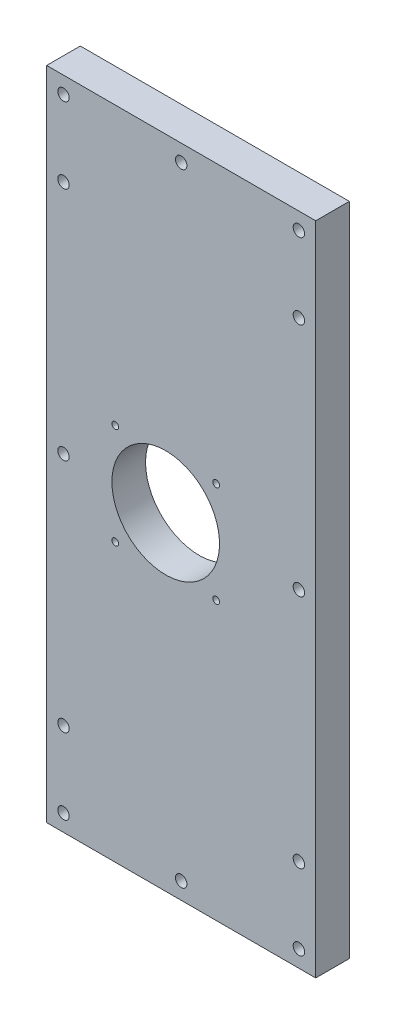
SolidWorks part; units mm, degrees
material "AISI 1020"
ref_plane "Ebene vorne" through (0, 0, 0) normal (0, 0, 1) x (1, 0, 0)
ref_plane "Ebene oben" through (0, 0, 0) normal (0, 1, 0) x (1, 0, 0)
ref_plane "Ebene rechts" through (0, 0, 0) normal (1, 0, 0) x (0, 0, -1)
sketch "Skizze1" plane through (0, 0, 0) normal (0, 0, 1) x (1, 0, 0)
  line L1 (-69.0594, 70.0995) -> (10.9406, 70.0995)
  line L2 (-69.0594, 70.0995) -> (-69.0594, -124.9005)
  line L3 (-69.0594, -124.9005) -> (10.9406, -124.9005)
  line L4 (10.9406, 70.0995) -> (10.9406, -124.9005)
  dimension "D1" = 195
  dimension "D2" = 80
extrude "Aufsatz-Linear austragen1" add sketch "Skizze1" against normal blind 10
sketch "Skizze2" plane through (0, 0, -10) normal (0, 0, -1) x (-1, 0, 0)
  line L0 (33.6594, 70.0995) -> (33.6594, -124.9005) construction
  line L1 (-10.9406, 70.0995) -> (69.0594, 70.0995) construction
  line L2 (69.0594, -124.9005) -> (-10.9406, -124.9005) construction
  line L3 (33.6594, -27.4005) -> (69.0594, -27.4005) construction
  line L4 (69.0594, 70.0995) -> (69.0594, -124.9005) construction
  line L5 (18.6594, -12.4005) -> (48.6594, -12.4005) construction
  line L6 (48.6594, -12.4005) -> (48.6594, -42.4005) construction
  line L7 (48.6594, -42.4005) -> (18.6594, -42.4005) construction
  line L8 (18.6594, -42.4005) -> (18.6594, -12.4005) construction
  line L9 (18.6594, -12.4005) -> (48.6594, -42.4005) construction
  circle A0 centre (18.6594, -12.4005) radius 1
  circle A1 centre (48.6594, -12.4005) radius 1
  circle A2 centre (18.6594, -42.4005) radius 1
  circle A3 centre (48.6594, -42.4005) radius 1
  circle A4 centre (33.6594, -27.4005) radius 16
  point P22 (33.6594, -27.4005)
  dimension "D1" = 30
  dimension "D3" = 2
  dimension "D2" = 30
  dimension "D4" = 35.4
extrude "Schnitt-Linear austragen1" cut sketch "Skizze2" against normal blind 10
sketch "Skizze3" plane through (0, 0, -10) normal (0, 0, -1) x (-1, 0, 0)
  line L0 (-5.9406, 65.0995) -> (64.0594, 65.0995) construction
  line L1 (29.0594, 65.0995) -> (29.0594, 70.0995) construction
  line L2 (-10.9406, 70.0995) -> (69.0594, 70.0995) construction
  line L3 (69.0594, 70.0995) -> (69.0594, -124.9005) construction
  line L4 (-5.9406, -119.9005) -> (64.0594, -119.9005) construction
  line L5 (29.0594, -119.9005) -> (29.0594, -124.9005) construction
  line L6 (69.0594, -124.9005) -> (-10.9406, -124.9005) construction
  line L7 (-5.9406, 42.5995) -> (-5.9406, -27.4005) construction
  line L8 (-5.9406, 42.5995) -> (-5.9406, 65.0995) construction
  line L9 (-5.9406, -27.4005) -> (-5.9406, -97.4005) construction
  line L10 (64.0594, 42.5995) -> (64.0594, 65.0995) construction
  line L11 (64.0594, -97.4005) -> (64.0594, -27.4005) construction
  line L12 (-5.9406, -97.4005) -> (-5.9406, -119.9005) construction
  line L13 (64.0594, -97.4005) -> (64.0594, -119.9005) construction
  line L15 (64.0594, -27.4005) -> (64.0594, 42.5995) construction
  circle A0 centre (29.0594, 65.0995) radius 3.5
  circle A1 centre (-5.9406, 65.0995) radius 3.5
  circle A2 centre (64.0594, 65.0995) radius 3.5
  circle A3 centre (29.0594, -119.9005) radius 3.5
  circle A4 centre (-5.9406, -119.9005) radius 3.5
  circle A5 centre (64.0594, -119.9005) radius 3.5
  circle A6 centre (-5.9406, 42.5995) radius 3.5
  circle A7 centre (-5.9406, -27.4005) radius 3.5
  circle A9 centre (-5.9406, -97.4005) radius 3.5
  circle A10 centre (64.0594, -97.4005) radius 3.5
  circle A12 centre (64.0594, -27.4005) radius 3.5
  circle A13 centre (64.0594, 42.5995) radius 3.5
  dimension "D3" = 7
  dimension "D1" = 5
  dimension "D2" = 5
  dimension "D4" = 70
extrude "Schnitt-Linear austragen2" cut sketch "Skizze3" against normal blind 5
sketch "Skizze6" plane through (0, 0, 0) normal (0, 0, 1) x (1, 0, 0)
  line L0 (-64.0594, 65.0995) -> (-64.0594, 42.5995) construction
  line L1 (10.9406, -124.9005) -> (10.9406, 70.0995) construction
  line L2 (-64.0594, 42.5995) -> (-64.0594, -27.4005) construction
  line L3 (-64.0594, -27.4005) -> (-64.0594, -97.4005) construction
  line L4 (-64.0594, -97.4005) -> (-64.0594, -119.9005) construction
  line L5 (-64.0594, 65.0995) -> (5.9406, 65.0995) construction
  line L6 (5.9406, -119.9005) -> (5.9406, -97.4005) construction
  line L7 (5.9406, -97.4005) -> (5.9406, -27.4005) construction
  line L8 (5.9406, -27.4005) -> (5.9406, 42.5995) construction
  line L10 (5.9406, 42.5995) -> (5.9406, 65.0995) construction
  line L11 (-64.0594, -119.9005) -> (5.9406, -119.9005) construction
  line L12 (10.9406, 70.0995) -> (-69.0594, 70.0995) construction
  line L14 (-29.0594, 65.0995) -> (-29.0594, 70.0995) construction
  line L15 (-69.0594, -124.9005) -> (10.9406, -124.9005) construction
  circle A0 centre (-64.0594, 65.0995) radius 1.7
  circle A1 centre (-29.0594, 65.0995) radius 1.7
  circle A2 centre (5.9406, 65.0995) radius 1.7
  circle A3 centre (-64.0594, 42.5995) radius 1.7
  circle A5 centre (-64.0594, -27.4005) radius 1.7
  circle A6 centre (-64.0594, -97.4005) radius 1.7
  circle A7 centre (-64.0594, -119.9005) radius 1.7
  circle A8 centre (5.9406, -119.9005) radius 1.7
  circle A9 centre (5.9406, -97.4005) radius 1.7
  circle A10 centre (5.9406, -27.4005) radius 1.7
  circle A12 centre (5.9406, 42.5995) radius 1.7
  circle A13 centre (-29.0594, -119.9005) radius 1.7
  dimension "D2" = 3.4
  dimension "D1" = 5
  dimension "D3" = 5
  dimension "D4" = 70
  dimension "D5" = 5
extrude "Schnitt-Linear austragen4" cut sketch "Skizze6" against normal blind 5
